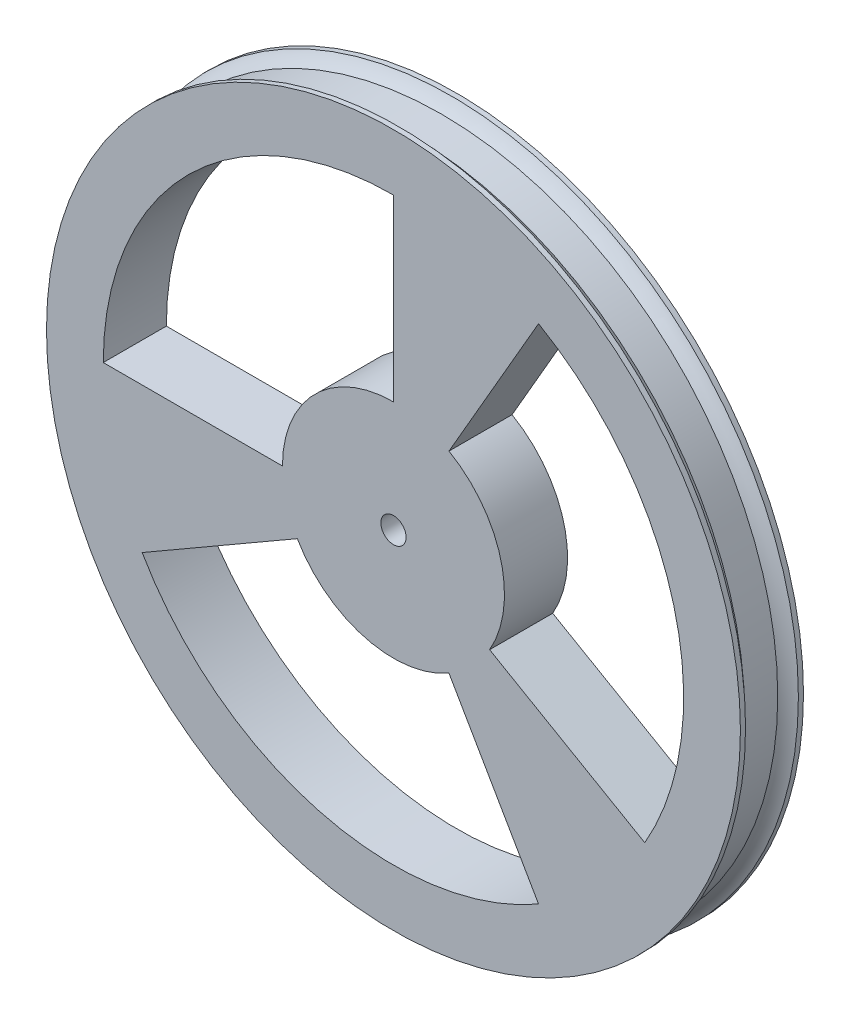
SolidWorks part; units mm, degrees
ref_plane "Plano frontal" through (0, 0, 0) normal (0, 0, 1) x (1, 0, 0)
ref_plane "Plano superior" through (0, 0, 0) normal (0, 1, 0) x (1, 0, 0)
ref_plane "Plano direito" through (0, 0, 0) normal (1, 0, 0) x (0, 0, -1)
sketch "Esboço1" plane through (0, 0, 0) normal (0, 0, 1) x (1, 0, 0)
  circle A0 centre (0, 0) radius 27.5
extrude "Ressalto-extrusão1" add sketch "Esboço1" along normal blind 5 contours A0
sketch "Esboço3" plane through (0, 0, 0) normal (0, 0, -1) x (-1, 0, 0)
  circle A0 centre (0, 0) radius 27.5 construction
  point P0 (0, 27.5)
ref_plane "Plano1" through (0, 0, 5) normal (0, 0, 1) x (1, 0, 0)
sketch "Esboço4" plane through (0, 0, 5) normal (0, 0, 1) x (1, 0, 0)
  circle A0 centre (0, 0) radius 27.5 construction
  point P0 (0, 27.5)
ref_plane "Plano2" through (0, 27.5, 0) normal (0, 1, 0) x (1, 0, 0)
sketch "Esboço5" plane through (0, 27.5, 0) normal (0, 1, 0) x (1, 0, 0)
  line L0 (0, -5) -> (0, 0)
sketch "Esboço6" plane through (0, 0, 5) normal (0, 0, 1) x (1, 0, 0)
  line L0 (0, 30.2609) -> (0, 27.5)
ref_plane "Plano3" through (0, 0, 0) normal (1, 0, 0) x (0, 0, -1)
sketch "Esboço7" plane through (0, 0, 0) normal (1, 0, 0) x (0, 0, -1)
  line L0 (-2.5, 27.5) -> (-2.5, 29.7938) construction
  line L1 (-5, 27.5) -> (0, 27.5) construction
  line L2 (-3.8085, 26.6497) -> (-1.1915, 26.6497)
  circle A0 centre (-2.5, 28.6469) radius 2.3877
ref_axis "Eixo1" through (0, 0, 5) along (0, 0, -1)
revolve "Corte-Revolução4" cut sketch "Esboço7" angle 360 about axis through (0, 0, 5) along (0, 0, -1) region at (0, 28.7336, 2.5)
sketch "Esboço9" plane through (0, 0, 5) normal (0, 0, 1) x (1, 0, 0)
  circle A0 centre (0, 0) radius 1
  dimension "D1" = 2
extrude "Corte-extrusão1" cut sketch "Esboço9" against normal blind 5
sketch "Esboço11" plane through (0, 0, 0) normal (0, 0, -1) x (-1, 0, 0)
  circle A0 centre (0, 0) radius 24.1119
sketch "Esboço10" plane through (0, 0, 5) normal (0, 0, 1) x (1, 0, 0)
  line L0 (0, 8.8) -> (0, 23)
  line L1 (4.4, 7.621) -> (11.5, 19.9186)
  line L2 (7.621, -4.4) -> (19.9186, -11.5)
  line L3 (4.4, -7.621) -> (11.5, -19.9186)
  line L4 (-7.621, -4.4) -> (-19.9186, -11.5)
  line L5 (-8.8, 0) -> (-23, 0)
  circle A0 centre (0, 0) radius 8.8
  arc A1 (0, 8.8) -> (-8.8, 0) centre (0, 0) ccw
  arc A2 (-8.8, 0) -> (-7.621, -4.4) centre (0, 0) ccw
  arc A3 (-7.621, -4.4) -> (4.4, -7.621) centre (0, 0) ccw
  arc A4 (4.4, -7.621) -> (7.621, -4.4) centre (0, 0) ccw
  arc A5 (7.621, -4.4) -> (4.4, 7.621) centre (0, 0) ccw
  circle A6 centre (0, 0) radius 23
  point P3 (0, 8.8)
  point P11 (4.4, 7.621)
extrude "Corte-extrusão2" cut sketch "Esboço10" against normal blind 5 contours L0 A6 L5 A0 | L2 A6 L1 A0 | L4 A6 L3 A0 region at (-10.795, 10.795, 5) region at (14.7463, 3.9513, 5) region at (-3.9513, -14.7463, 5)
